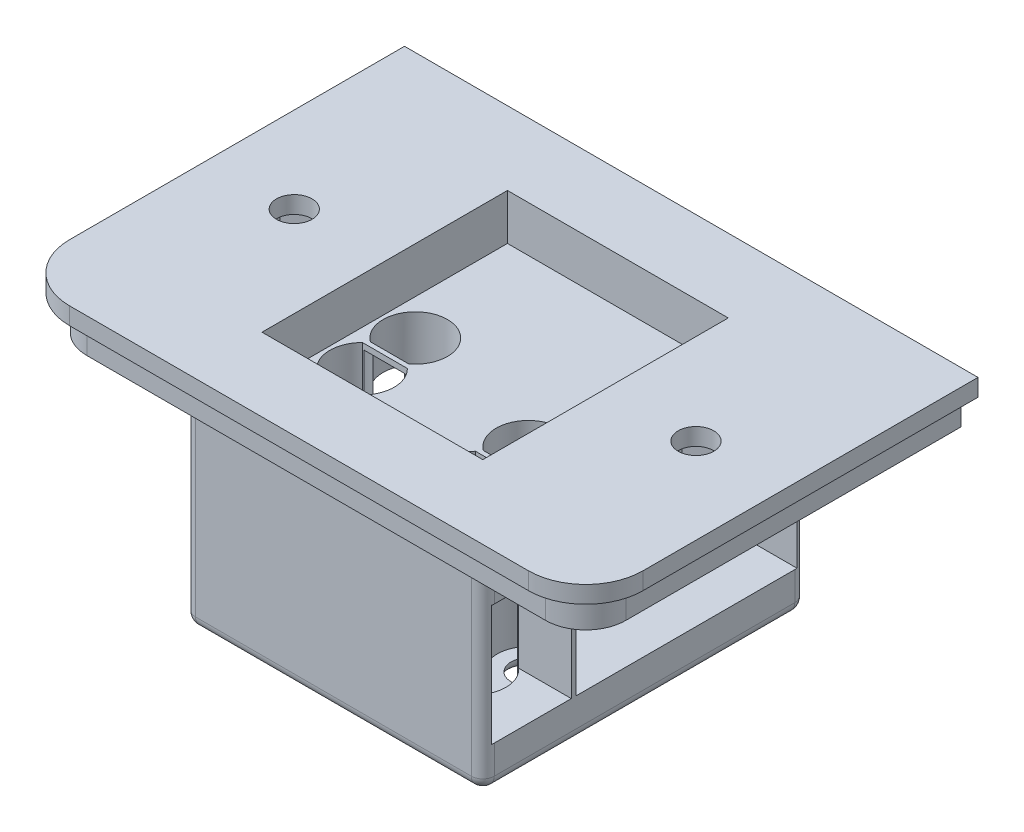
SolidWorks part; units mm, degrees
note: The reader was unsure of these and kept them because the rebuilt part matched: shared geometry of "Sketch6<4>", "Sketch6<5>".
ref_plane "Front Plane" through (0, 0, 0) normal (0, 0, 1) x (1, 0, 0)
ref_plane "Top Plane" through (0, 0, 0) normal (0, 1, 0) x (1, 0, 0)
ref_plane "Right Plane" through (0, 0, 0) normal (1, 0, 0) x (0, 0, -1)
sketch "Sketch1" plane through (0, 0, 0) normal (0, 1, 0) x (1, 0, 0)
  line L1 (0, 0) -> (26.05, 0)
  line L2 (0, 0) -> (0, 28.2)
  line L3 (0, 28.2) -> (26.05, 28.2)
  line L4 (26.05, 0) -> (26.05, 28.2)
  dimension "D1" = 26.05
  dimension "D2" = 28.2
extrude "Boss-Extrude1" add sketch "Sketch1" against normal blind 8
sketch "Sketch2" plane through (0, 0, 0) normal (0, 1, 0) x (1, 0, 0)
  line L1 (3.4, 3.4) -> (22.65, 3.4)
  line L2 (3.4, 3.4) -> (3.4, 24.8)
  line L3 (3.4, 24.8) -> (22.65, 24.8)
  line L4 (22.65, 3.4) -> (22.65, 24.8)
  line L8 (26.05, 28.2) -> (0, 28.2) construction
  line L10 (26.05, 0) -> (26.05, 28.2) construction
  dimension "D1" = 21.4
  dimension "D2" = 19.25
  dimension "D3" = 3.4
  dimension "D4" = 3.4
extrude "Cut-Extrude1" cut sketch "Sketch2" against normal blind 4
sketch "Sketch4" plane through (0, -4, 0) normal (0, 1, 0) x (1, 0, 0)
  line L0 (3.4, 24.8) -> (22.65, 3.4) construction
  line L1 (22.65, 24.8) -> (3.4, 3.4) construction
  line L3 (19.45, 6.57) -> (19.85, 6.57) construction
  line L4 (19.45, 6.57) -> (19.45, 6.97) construction
  line L5 (19.45, 6.97) -> (19.85, 6.97) construction
  line L6 (19.85, 6.57) -> (19.85, 6.97) construction
  line L7 (19.45, 6.57) -> (19.85, 6.97) construction
  line L8 (19.45, 6.97) -> (19.85, 6.57) construction
  line L9 (19.45, 9.11) -> (19.85, 9.11) construction
  line L10 (19.45, 9.11) -> (19.45, 9.51) construction
  line L11 (19.45, 9.51) -> (19.85, 9.51) construction
  line L12 (19.85, 9.11) -> (19.85, 9.51) construction
  line L13 (19.45, 9.11) -> (19.85, 9.51) construction
  line L14 (19.45, 9.51) -> (19.85, 9.11) construction
  line L15 (6.32, 9.85) -> (6.72, 9.85) construction
  line L16 (6.32, 9.85) -> (6.32, 10.25) construction
  line L17 (6.32, 10.25) -> (6.72, 10.25) construction
  line L18 (6.72, 9.85) -> (6.72, 10.25) construction
  line L19 (6.32, 9.85) -> (6.72, 10.25) construction
  line L20 (6.32, 10.25) -> (6.72, 9.85) construction
  line L21 (6.32, 12.39) -> (6.72, 12.39) construction
  line L22 (6.32, 12.39) -> (6.32, 12.79) construction
  line L23 (6.32, 12.79) -> (6.72, 12.79) construction
  line L24 (6.72, 12.39) -> (6.72, 12.79) construction
  line L25 (6.32, 12.39) -> (6.72, 12.79) construction
  line L26 (6.32, 12.79) -> (6.72, 12.39) construction
  line L27 (18.025, 4.015) -> (21.275, 4.015)
  line L28 (18.025, 4.015) -> (18.025, 7.415)
  line L29 (18.025, 7.415) -> (21.275, 7.415)
  line L30 (21.275, 4.015) -> (21.275, 7.415)
  line L31 (4.895, 11.945) -> (8.145, 11.945)
  line L32 (4.895, 11.945) -> (4.895, 15.345)
  line L33 (18.025, 8.665) -> (21.275, 8.665)
  line L34 (18.025, 8.665) -> (18.025, 12.065)
  line L35 (18.025, 12.065) -> (21.275, 12.065)
  line L36 (21.275, 8.665) -> (21.275, 12.065)
  line L37 (4.895, 15.345) -> (8.145, 15.345)
  line L38 (8.145, 11.945) -> (8.145, 15.345)
  line L39 (4.895, 7.295) -> (8.145, 7.295)
  line L40 (4.895, 7.295) -> (4.895, 10.695)
  line L41 (4.895, 10.695) -> (8.145, 10.695)
  line L42 (8.145, 7.295) -> (8.145, 10.695)
  line L45 (22.25, 3.8) -> (3.8, 3.8) construction
  line L46 (22.25, 3.8) -> (22.25, 24.4) construction
  line L47 (22.25, 24.4) -> (3.8, 24.4) construction
  line L48 (3.8, 3.8) -> (3.8, 24.4) construction
  line L49 (22.25, 3.8) -> (3.8, 24.4) construction
  line L50 (22.25, 24.4) -> (3.8, 3.8) construction
  point P8 (19.65, 6.77)
  point P13 (6.52, 10.05)
  point P15 (19.65, 9.31)
  point P24 (6.52, 12.59)
  point P29 (19.65, 9.31)
  point P30 (19.65, 6.77)
  point P41 (19.65, 12.065)
  point P52 (6.52, 10.695)
  point P53 (13.025, 14.1)
  dimension "D3" = 0.4
  dimension "D4" = 0.4
  dimension "D5" = 2.54
  dimension "D6" = 2.72
  dimension "D7" = 6.25
  dimension "D8" = 0.4
  dimension "D9" = 0.4
  dimension "D10" = 2.54
  dimension "D11" = 3.4
  dimension "D12" = 3.25
  dimension "D13" = 1.25
  dimension "D14" = 0.645
  dimension "D15" = 1.25
  dimension "D16" = 3.25
  dimension "D17" = 3.4
  dimension "D18" = 0.645
  dimension "D19" = 2.97
  dimension "D20" = 20.6
  dimension "D21" = 18.45
  dimension "D22" = 2.6
extrude "Cut-Extrude4" cut sketch "Sketch4" against normal blind 1 and the other way through all
sketch "Sketch6" plane through (0, -5, 0) normal (0, 1, 0) x (1, 0, 0)
  line L0 (18.025, 7.415) -> (21.275, 4.015) construction
  line L1 (18.025, 4.015) -> (21.275, 7.415) construction
  line L2 (18.025, 12.065) -> (21.275, 8.665) construction
  line L3 (18.025, 8.665) -> (21.275, 12.065) construction
  line L4 (4.895, 7.295) -> (8.145, 10.695) construction
  line L5 (8.145, 7.295) -> (4.895, 10.695) construction
  line L6 (8.145, 11.945) -> (4.895, 15.345) construction
  line L7 (4.895, 11.945) -> (8.145, 15.345) construction
  arc A0 (5.1473, 11.32) -> (7.8927, 11.32) centre (6.52, 8.995) ccw
  arc A1 (7.8927, 11.32) -> (5.1473, 11.32) centre (6.52, 13.645) ccw
  arc A2 (21.0227, 8.04) -> (18.2773, 8.04) centre (19.65, 10.365) ccw
  arc A3 (18.2773, 8.04) -> (21.0227, 8.04) centre (19.65, 5.715) ccw
  point P37 (6.52, 8.995)
  point P38 (6.52, 13.645)
  dimension "D1" = 5.4
extrude "Cut-Extrude7" cut sketch "Sketch6" against normal blind 16.5 and the other way blind 0.5
sketch "Sketch7" plane through (0, -8, 0) normal (0, -1, 0) x (1, 0, 0)
  line L0 (0, 0) -> (26.05, 0) construction
  line L1 (6.22, 0) -> (19.95, 0)
  line L2 (6.22, 0) -> (6.22, -28.2)
  line L3 (6.22, -28.2) -> (19.95, -28.2)
  line L4 (19.95, 0) -> (19.95, -28.2)
  line L5 (18.025, -8.665) -> (21.275, -12.065) construction
  line L6 (18.025, -12.065) -> (21.275, -8.665) construction
  line L7 (4.895, -15.345) -> (8.145, -11.945) construction
  line L8 (4.895, -11.945) -> (8.145, -15.345) construction
  line L9 (26.05, -28.2) -> (0, -28.2) construction
  point P22 (19.65, -10.365)
  point P23 (6.52, -13.645)
  dimension "D2" = 0.3
  dimension "D3" = 0.3
extrude "Boss-Extrude2" add sketch "Sketch7" along normal blind 11
extrude "Cut-Extrude8" cut sketch "Sketch6<4>" against normal up to next
sketch "Sketch6<4>" plane through (0, -5, 0) normal (0, 1, 0) x (1, 0, 0) same geometry as "Sketch6"
sketch "Sketch8" plane through (0, -19, 0) normal (0, -1, 0) x (1, 0, 0)
  line L0 (19.95, 0) -> (19.95, -3.0317)
  line L1 (0, -28.2) -> (6.22, -28.2)
  line L2 (0, -28.2) -> (0, 0)
  line L3 (0, 0) -> (6.22, 0)
  line L4 (26.05, -28.2) -> (26.05, 0)
  line L5 (19.95, -13.0483) -> (19.95, -28.2)
  line L7 (6.22, -28.2) -> (6.22, -16.3283)
  line L8 (6.22, -6.3117) -> (6.22, 0)
  line L9 (19.95, 0) -> (26.05, 0)
  line L10 (19.95, -28.2) -> (26.05, -28.2)
  arc A0 (19.95, -3.0317) -> (18.2773, -8.04) centre (19.65, -5.715) ccw
  arc A1 (18.2773, -8.04) -> (19.95, -13.0483) centre (19.65, -10.365) ccw
  arc A2 (7.8927, -11.32) -> (6.22, -6.3117) centre (6.52, -8.995) ccw
  arc A3 (6.22, -16.3283) -> (7.8927, -11.32) centre (6.52, -13.645) ccw
extrude "Boss-Extrude3" add sketch "Sketch8" against normal blind 0.5
sketch "Sketch9" plane through (0, -19, 0) normal (0, -1, 0) x (1, 0, 0)
  line L1 (0, -28.2) -> (26.05, -28.2)
  line L2 (0, -28.2) -> (0, 0)
  line L3 (0, 0) -> (26.05, 0)
  line L4 (26.05, -28.2) -> (26.05, 0)
extrude "Boss-Extrude4" add sketch "Sketch9" along normal blind 3
sketch "Sketch10" plane through (0, -18.5, 0) normal (0, 1, 0) x (1, 0, 0)
  line L0 (6.22, 0) -> (6.22, 28.2) construction
  line L1 (0, 28.2) -> (6.22, 28.2)
  line L2 (18.025, 12.065) -> (21.275, 8.665) construction
  line L3 (0, 28.2) -> (0, 0) construction
  line L4 (26.05, 7.7188) -> (17.8403, 7.7188)
  line L5 (26.05, 0) -> (26.05, 28.2) construction
  line L6 (0, 28.2) -> (0, 27.4)
  line L7 (18.1519, 8.1188) -> (26.05, 8.1188)
  line L8 (0, 10.9988) -> (0, 11.3988)
  line L9 (0, 11.3988) -> (8.0181, 11.3988)
  line L10 (0, 27.4) -> (6.22, 27.4)
  line L11 (0, 10.9988) -> (8.3297, 10.9988)
  line L12 (26.05, 8.1188) -> (26.05, 7.7188)
  line L13 (6.22, 28.2) -> (6.22, 27.4)
  line L14 (19.95, 0) -> (19.95, 28.2) construction
  line L15 (0, 0) -> (6.22, 0)
  line L16 (0, 0) -> (0, 0.8)
  line L17 (0, 0.8) -> (6.22, 0.8)
  line L18 (6.22, 0) -> (6.22, 0.8)
  line L19 (26.05, 0) -> (19.95, 0)
  line L20 (26.05, 0) -> (26.05, 0.8)
  line L21 (26.05, 0.8) -> (19.95, 0.8)
  line L22 (19.95, 0) -> (19.95, 0.8)
  line L24 (26.05, 28.2) -> (19.95, 28.2)
  line L25 (26.05, 28.2) -> (26.05, 27.4)
  line L26 (26.05, 27.4) -> (19.95, 27.4)
  line L27 (19.95, 28.2) -> (19.95, 27.4)
  arc A0 (18.1519, 8.1188) -> (18.2773, 8.04) centre (19.65, 10.365) ccw
  arc A1 (18.2773, 8.04) -> (17.8403, 7.7188) centre (19.65, 5.715) ccw
  arc A4 (21.0227, 8.04) -> (18.2773, 8.04) centre (19.65, 10.365) ccw construction
  arc A5 (18.2773, 8.04) -> (21.0227, 8.04) centre (19.65, 5.715) ccw construction
  arc A6 (7.8927, 11.32) -> (8.0181, 11.3988) centre (6.52, 13.645) ccw
  arc A7 (8.3297, 10.9988) -> (7.8927, 11.32) centre (6.52, 8.995) ccw
  dimension "D5" = 0.8
  dimension "D6" = 0.8
  dimension "D1" = 0.4
  dimension "D2" = 7.8981
  dimension "D3" = 0.4
  dimension "D4" = 8.0181
  dimension "D7" = 0.8
  dimension "D8" = 0.8
extrude "Boss-Extrude6" add sketch "Sketch10" along normal up to next (14 mm away) and the other way up to next (3.5 mm away)
extrude "Cut-Extrude9" cut sketch "Sketch6<5>" against normal blind 16 and the other way blind 0.5
sketch "Sketch6<5>" plane through (0, -5, 0) normal (0, 1, 0) x (1, 0, 0) same geometry as "Sketch6"
sketch "Sketch11" plane through (0, -21, 0) normal (0, 1, 0) x (1, 0, 0)
  circle A0 centre (6.52, 13.645) radius 1.5
  circle A1 centre (6.52, 8.995) radius 1.5
  circle A2 centre (19.65, 10.365) radius 1.5
  circle A3 centre (19.65, 5.715) radius 1.5
  dimension "D1" = 3
extrude "Cut-Extrude10" cut sketch "Sketch11" against normal up to next
fillet "Fillet1" radius 0.5 16 edges at (18.025, -4.25, -8.665) (8.145, -4.25, -7.295) (8.145, -4.25, -11.945) (21.275, -4.25, -4.015) (21.275, -4.25, -8.665) (4.895, -4.25, -11.945) (18.025, -4.25, -4.015) (4.895, -4.25, -7.295) (21.275, -4.25, -7.415) (21.275, -4.25, -12.065) (8.145, -4.25, -10.695) (8.145, -4.25, -15.345) (18.025, -4.25, -7.415) (18.025, -4.25, -12.065) (4.895, -4.25, -10.695) (4.895, -4.25, -15.345)
sketch "Sketch12" plane through (0, 0, 0) normal (0, 1, 0) x (1, 0, 0)
  line L0 (13.025, 0) -> (13.025, 28.2) construction
  line L1 (0, 0) -> (26.05, 0)
  line L2 (0, 0) -> (0, 28.2)
  line L3 (0, 28.2) -> (26.05, 28.2)
  line L4 (26.05, 0) -> (26.05, 28.2)
  line L6 (-6.975, -3) -> (33.025, -3)
  line L7 (-11.975, 2) -> (-11.975, 92)
  line L8 (-6.975, 97) -> (33.025, 97)
  line L9 (38.025, 2) -> (38.025, 92)
  arc A0 (-11.975, 92) -> (-6.975, 97) centre (-6.975, 92) cw
  arc A1 (33.025, 97) -> (38.025, 92) centre (33.025, 92) cw
  arc A2 (33.025, -3) -> (38.025, 2) centre (33.025, 2) ccw
  arc A3 (-6.975, -3) -> (-11.975, 2) centre (-6.975, 2) cw
  point P12 (13.025, -3)
  point P15 (-11.975, 97)
  point P22 (-11.975, -3)
  dimension "D3" = 5
  dimension "D1" = 50
  dimension "D2" = 100
  dimension "D4" = 3
extrude "Boss-Extrude7" add sketch "Sketch12" against normal blind 1.5
sketch "Sketch13" plane through (0, -1.5, 0) normal (0, -1, 0) x (1, 0, 0)
  line L0 (-6.975, 3) -> (33.025, 3) construction
  line L1 (-6.975, -97) -> (33.025, -97) construction
  line L2 (-11.975, -92) -> (-11.975, -2) construction
  line L3 (-6.975, 3) -> (33.025, 3) construction
  line L4 (38.025, -92) -> (38.025, -2) construction
  line L5 (33.025, -97) -> (-6.975, -97) construction
  line L6 (38.025, -2) -> (38.025, -92) construction
  line L7 (-11.975, -92) -> (-11.975, -2) construction
  line L8 (-6.975, -95.5) -> (33.025, -95.5)
  line L9 (36.525, -92) -> (36.525, -2)
  line L10 (-6.975, 1.5) -> (33.025, 1.5)
  line L11 (-10.475, -92) -> (-10.475, -2)
  line L12 (-8.975, -92) -> (-8.975, -2)
  line L13 (-6.975, 0) -> (33.025, 0)
  line L14 (35.025, -92) -> (35.025, -2)
  line L15 (-6.975, -94) -> (33.025, -94)
  arc A0 (-11.975, -2) -> (-6.975, 3) centre (-6.975, -2) cw construction
  arc A1 (33.025, 3) -> (38.025, -2) centre (33.025, -2) cw construction
  arc A2 (33.025, -97) -> (38.025, -92) centre (33.025, -92) ccw construction
  arc A3 (-6.975, -97) -> (-11.975, -92) centre (-6.975, -92) cw construction
  arc A4 (33.025, -95.5) -> (36.525, -92) centre (33.025, -92) ccw
  arc A5 (33.025, 1.5) -> (36.525, -2) centre (33.025, -2) cw
  arc A6 (-10.475, -2) -> (-6.975, 1.5) centre (-6.975, -2) cw
  arc A7 (-6.975, -95.5) -> (-10.475, -92) centre (-6.975, -92) cw
  arc A8 (-6.975, -94) -> (-8.975, -92) centre (-6.975, -92) cw
  arc A9 (-8.975, -2) -> (-6.975, 0) centre (-6.975, -2) cw
  arc A10 (33.025, 0) -> (35.025, -2) centre (33.025, -2) cw
  arc A11 (33.025, -94) -> (35.025, -92) centre (33.025, -92) ccw
  dimension "D1" = 5
  dimension "D2" = 1.5
  dimension "D3" = 1.5
extrude "Boss-Extrude8" add sketch "Sketch13" along normal blind 3
fillet "Fillet3" radius 1 4 edges at (0, -13.25, 0) (26.05, -13.25, 0) (0, -11.75, -28.2) (26.05, -11.75, -28.2)
sketch "Sketch15" plane through (0, -8, 0) normal (0, -1, 0) x (1, 0, 0)
  line L0 (4.5642, -10.9988) -> (8.4758, -10.9988)
  line L1 (8.1916, -11.3988) -> (4.8484, -11.3988)
  line L2 (26.05, -7.7188) -> (21.4597, -7.7188) construction
  line L3 (17.6942, -7.7188) -> (21.6058, -7.7188)
  line L4 (21.3216, -8.1188) -> (17.9784, -8.1188)
  arc A1 (21.6058, -7.7188) -> (17.6942, -7.7188) centre (19.65, -5.715) ccw
  arc A3 (17.9784, -8.1188) -> (21.3216, -8.1188) centre (19.65, -10.365) ccw
  arc A5 (4.8484, -11.3988) -> (8.1916, -11.3988) centre (6.52, -13.645) ccw
  arc A7 (8.4758, -10.9988) -> (4.5642, -10.9988) centre (6.52, -8.995) ccw
  dimension "D1" = 5.6
extrude "Cut-Extrude12" cut sketch "Sketch15" against normal up to surface (4 mm away) up to face at (6.52, -4, -13.645)
sketch "Sketch16" plane through (0, -1.5, 0) normal (0, -1, 0) x (1, 0, 0)
  line L1 (0, -28.2) -> (-8.975, -28.2) construction
  line L2 (0, -28.2) -> (0, 0) construction
  line L3 (0, 0) -> (-8.975, 0) construction
  line L4 (-8.975, -28.2) -> (-8.975, 0) construction
  line L6 (-8.975, -28.2) -> (0, 0) construction
  line L7 (0, -28.2) -> (-8.975, 0) construction
  line L8 (25.05, 0) -> (1, 0) construction
  line L9 (13.025, 0) -> (13.025, -28.2) construction
  line L15 (-6.975, 0) -> (0, 0) construction
  line L19 (-8.975, -2) -> (-8.975, -92) construction
  line L20 (0, -27.2) -> (0, 0) construction
  line L21 (1, -28.2) -> (25.05, -28.2) construction
  circle A0 centre (-4.4875, -14.1) radius 1.55
  circle A1 centre (30.5375, -14.1) radius 1.55
  dimension "D1" = 3.1
extrude "Cut-Extrude13" cut sketch "Sketch16" against normal up to next
sketch "Sketch17" plane through (0, -1.5, 0) normal (0, -1, 0) x (1, 0, 0)
  line L0 (-8.975, -28.2) -> (0, 0) construction
  line L1 (-1.5875, -12.4257) -> (-4.4875, -10.7514)
  line L2 (-4.4875, -10.7514) -> (-7.3875, -12.4257)
  line L3 (-7.3875, -12.4257) -> (-7.3875, -15.7743)
  line L4 (-7.3875, -15.7743) -> (-4.4875, -17.4486)
  line L5 (-4.4875, -17.4486) -> (-1.5875, -15.7743)
  line L6 (-1.5875, -15.7743) -> (-1.5875, -12.4257)
  line L7 (-8.975, -28.2) -> (-8.975, 0) construction
  line L8 (0, -19.1) -> (-8.975, -19.1)
  line L9 (0, -19.1) -> (0, -9.1)
  line L10 (0, -9.1) -> (-8.975, -9.1)
  line L11 (-8.975, -19.1) -> (-8.975, -9.1)
  line L12 (0, -19.1) -> (-8.975, -9.1) construction
  line L13 (0, -9.1) -> (-8.975, -19.1) construction
  line L14 (13.025, -28.2) -> (13.025, 0) construction
  line L15 (26.05, -9.1) -> (35.025, -19.1) construction
  line L16 (26.05, -19.1) -> (35.025, -9.1) construction
  line L17 (35.025, -19.1) -> (35.025, -9.1)
  line L18 (26.05, -9.1) -> (35.025, -9.1)
  line L19 (26.05, -19.1) -> (26.05, -9.1)
  line L20 (26.05, -19.1) -> (35.025, -19.1)
  line L21 (27.6375, -15.7743) -> (27.6375, -12.4257)
  line L22 (30.5375, -17.4486) -> (27.6375, -15.7743)
  line L23 (33.4375, -15.7743) -> (30.5375, -17.4486)
  line L24 (33.4375, -12.4257) -> (33.4375, -15.7743)
  line L25 (30.5375, -10.7514) -> (33.4375, -12.4257)
  line L26 (27.6375, -12.4257) -> (30.5375, -10.7514)
  circle A0 centre (-4.4875, -14.1) radius 2.9 construction
  circle A1 centre (30.5375, -14.1) radius 2.9 construction
  dimension "D1" = 5.8
  dimension "D2" = 10
extrude "Boss-Extrude9" add sketch "Sketch17" along normal up to surface (3 mm away) up to face at (13.025, -4.5, -47)
fillet "Fillet4" radius 0.5 5 edges at (-8.3892, -1.5, -0.5858) (-3.4875, -1.5, 0) (0, -1.5, -4.55) (-4.4875, -1.5, -9.1) (-8.975, -1.5, -5.55)
fillet "Fillet5" radius 0.5 12 edges at (34.4392, -1.5, -93.4142) (13.025, -1.5, -94) (-8.3892, -1.5, -93.4142) (-8.975, -1.5, -55.55) (-4.4875, -1.5, -19.1) (0, -1.5, -23.15) (0.2929, -1.5, -27.9071) (13.025, -1.5, -28.2) (25.7571, -1.5, -27.9071) (26.05, -1.5, -23.15) (30.5375, -1.5, -19.1) (35.025, -1.5, -55.55)
fillet "Fillet6" radius 0.5 5 edges at (29.5375, -1.5, 0) (34.4392, -1.5, -0.5858) (35.025, -1.5, -5.55) (30.5375, -1.5, -9.1) (26.05, -1.5, -4.55)
fillet "Fillet7" radius 1 12 edges at (25.7571, -22, -0.2929) (26.05, -22, -14.1) (25.7571, -22, -27.9071) (13.025, -22, -28.2) (0.2929, -22, -27.9071) (0, -22, -14.1) (0.2929, -22, -0.2929) (13.025, -22, 0) (6.52, -22, -7.495) (19.65, -22, -4.215) (19.65, -22, -8.865) (6.52, -22, -12.145)
sketch "Sketch19" plane through (0, 0, 0) normal (0, 1, 0) x (1, 0, 0)
  line L0 (33.025, 97) -> (-6.975, 97) construction
  line L1 (-11.975, 97) -> (38.025, 97)
  line L2 (-11.975, 97) -> (-11.975, 31.2)
  line L3 (-11.975, 31.2) -> (38.025, 31.2)
  line L4 (38.025, 97) -> (38.025, 31.2)
  line L5 (-11.975, 92) -> (-11.975, 2) construction
  line L6 (38.025, 2) -> (38.025, 92) construction
  line L7 (1, 28.2) -> (25.05, 28.2) construction
  dimension "D1" = 3
extrude "Cut-Extrude15" cut sketch "Sketch19" against normal through all
